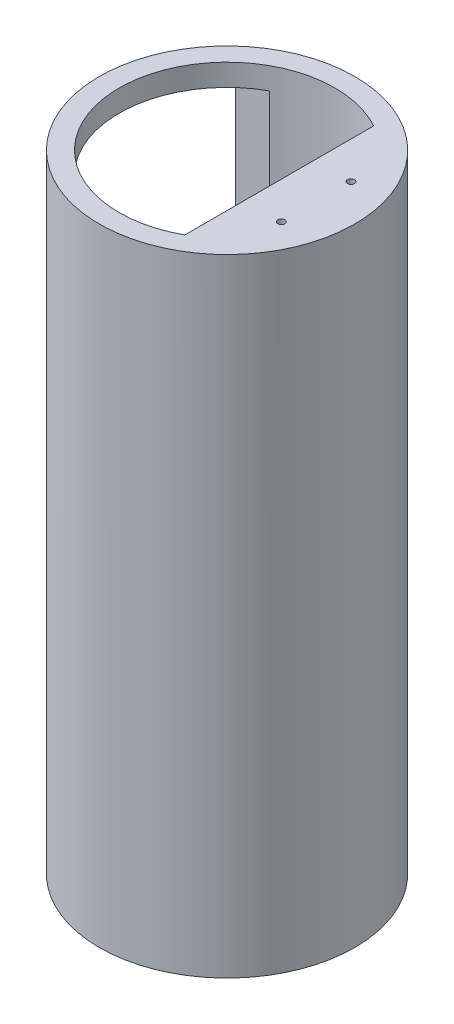
SolidWorks part; units mm, degrees
ref_plane "Front Plane" through (0, 0, 0) normal (0, 0, 1) x (1, 0, 0)
ref_plane "Top Plane" through (0, 0, 0) normal (0, 1, 0) x (1, 0, 0)
ref_plane "Right Plane" through (0, 0, 0) normal (1, 0, 0) x (0, 0, -1)
sketch "Sketch1" plane through (0, 0, 0) normal (0, 1, 0) x (1, 0, 0)
  circle A1 centre (0, 0) radius 46.609
  dimension "D1" = 93.218
extrude "Boss-Extrude1" add sketch "Sketch1" along normal blind 25.4
sketch "Sketch4" plane through (0, 25.4, 0) normal (0, 1, 0) x (1, 0, 0)
  line L0 (19.05, 42.5382) -> (19.05, -42.5382)
  circle A0 centre (0, 0) radius 46.609 construction
  arc A1 (19.05, 42.5382) -> (19.05, -42.5382) centre (0, 0) cw
  dimension "D1" = 19.05
extrude "Boss-Extrude2" add sketch "Sketch4" along normal blind 203.2
sketch "Sketch5" plane through (19.05, 0, 0) normal (-1, 0, 0) x (0, 0, 1)
  line L0 (-42.5382, 228.6) -> (42.5382, 228.6) construction
  line L1 (-26.67, 216.535) -> (26.67, 216.535)
  line L2 (-26.67, 216.535) -> (-26.67, 126.365)
  line L3 (-26.67, 126.365) -> (26.67, 126.365)
  line L4 (26.67, 216.535) -> (26.67, 126.365)
  line L6 (42.5382, 228.6) -> (42.5382, 25.4) construction
  circle A0 centre (-26.67, 216.535) radius 1.1049
  circle A1 centre (26.67, 216.535) radius 1.1049
  circle A2 centre (26.67, 126.365) radius 1.1049
  circle A3 centre (-26.67, 126.365) radius 1.1049
  point P4 (0, 216.535)
  point P7 (0, 228.6)
  point P10 (42.5382, 127)
  point P11 (26.67, 171.45)
  dimension "D5" = 2.2098
  dimension "D6" = 2.2098
  dimension "D7" = 2.2098
  dimension "D8" = 2.2098
  dimension "D1" = 0
  dimension "D2" = 44.45
  dimension "D3" = 90.17
  dimension "D4" = 53.34
extrude "Cut-Extrude1" cut sketch "Sketch5" against normal blind 38.1 contours L1 A0 L2 | L2 A0 L1 | L1 A1 L4 | L4 A1 L1 | A2 | A3 region at (19.05, 216.6913, -26.8263) region at (19.05, 216.0661, -26.2011) region at (19.05, 216.6913, 26.8263) region at (19.05, 216.0661, 26.2011)
sketch "Sketch9" plane through (0, 228.6, 0) normal (0, 1, 0) x (1, 0, 0)
  circle A0 centre (0, 0) radius 46.609
  circle A1 centre (0, 0) radius 39.37
  dimension "D1" = 93.218
  dimension "D2" = 78.74
extrude "Boss-Extrude5" add sketch "Sketch9" against normal up to surface (203.2 mm away) up to face at (-13.7795, 25.4, 0)
sketch "Sketch11" plane through (19.05, 0, 0) normal (-1, 0, 0) x (0, 0, 1)
  line L0 (-34.4542, 25.4) -> (-34.4542, 228.6) construction
  line L1 (-34.4542, 220.6179) -> (34.4542, 220.6179)
  line L2 (-34.4542, 220.6179) -> (-34.4542, 50.4379)
  line L3 (-34.4542, 50.4379) -> (34.4542, 50.4379)
  line L4 (34.4542, 220.6179) -> (34.4542, 50.4379)
  line L5 (34.4542, 228.6) -> (34.4542, 25.4) construction
  line L6 (-34.4542, 25.4) -> (34.4542, 25.4) construction
  line L7 (-34.4542, 162.56) -> (34.4542, 162.56)
  line L8 (-34.4542, 162.56) -> (-34.4542, 137.16)
  line L9 (-34.4542, 137.16) -> (34.4542, 137.16)
  line L10 (34.4542, 162.56) -> (34.4542, 137.16)
  line L12 (-34.4542, 50.4379) -> (34.4542, 50.4379)
  line L13 (-34.4542, 50.4379) -> (-34.4542, 25.4)
  line L14 (-34.4542, 25.4) -> (34.4542, 25.4)
  line L15 (34.4542, 50.4379) -> (34.4542, 25.4)
  circle M9 centre (-26.67, 126.365) radius 1.1049
  circle M10 centre (26.67, 126.365) radius 1.1049
  circle M11 centre (26.67, 216.535) radius 1.1049
  circle M12 centre (-26.67, 216.535) radius 1.1049
  line M13 (-34.4542, 228.6) -> (-34.4542, 25.4)
  line M15 (34.4542, 25.4) -> (34.4542, 228.6)
  dimension "D1" = 25.4
  dimension "D2" = 137.16
  dimension "D3" = 170.18
extrude "Cut-Extrude3" cut sketch "Sketch11" along normal blind 154.686 contours L7 L4 L1 M13 M11 M12 | M12 | L9 L3 M13 M15 M10 M9 | M11 | M10 | M9 | L13 L12 L15 L14 region at (19.05, 191.541, 0) region at (19.05, 93.7571, 0) region at (19.05, 126.365, -26.67) region at (19.05, 126.365, 26.67) region at (19.05, 216.535, 26.67) region at (19.05, 216.535, -26.67)
sketch "Sketch12" plane through (19.05, 0, 0) normal (-1, 0, 0) x (0, 0, 1)
  line L1 (-27.432, 117.7292) -> (27.432, 117.7292)
  line L2 (-27.432, 117.7292) -> (-27.432, 35.1792)
  line L3 (-27.432, 35.1792) -> (27.432, 35.1792)
  line L4 (27.432, 117.7292) -> (27.432, 35.1792)
  point P0 (0, 35.1792)
  dimension "D1" = 82.55
  dimension "D2" = 0
  dimension "D3" = 54.864
sketch "Sketch13" plane through (0, 228.6, 0) normal (0, 1, 0) x (1, 0, 0)
  circle A0 centre (32.512, 0) radius 3.0803
  circle A1 centre (32.512, -12.7) radius 1.27
  circle A2 centre (32.512, 12.7) radius 1.27
  dimension "D4" = 2.54
  dimension "D5" = 2.54
  dimension "D1" = 12.7
  dimension "D2" = 12.7
  dimension "D3" = 0
  dimension "D6" = 32.512
extrude "Cut-Extrude4" cut sketch "Sketch13" against normal blind 12.7 contours A1 | A2
extrude "Cut-Extrude5" cut sketch "Sketch12" against normal blind 2.54
